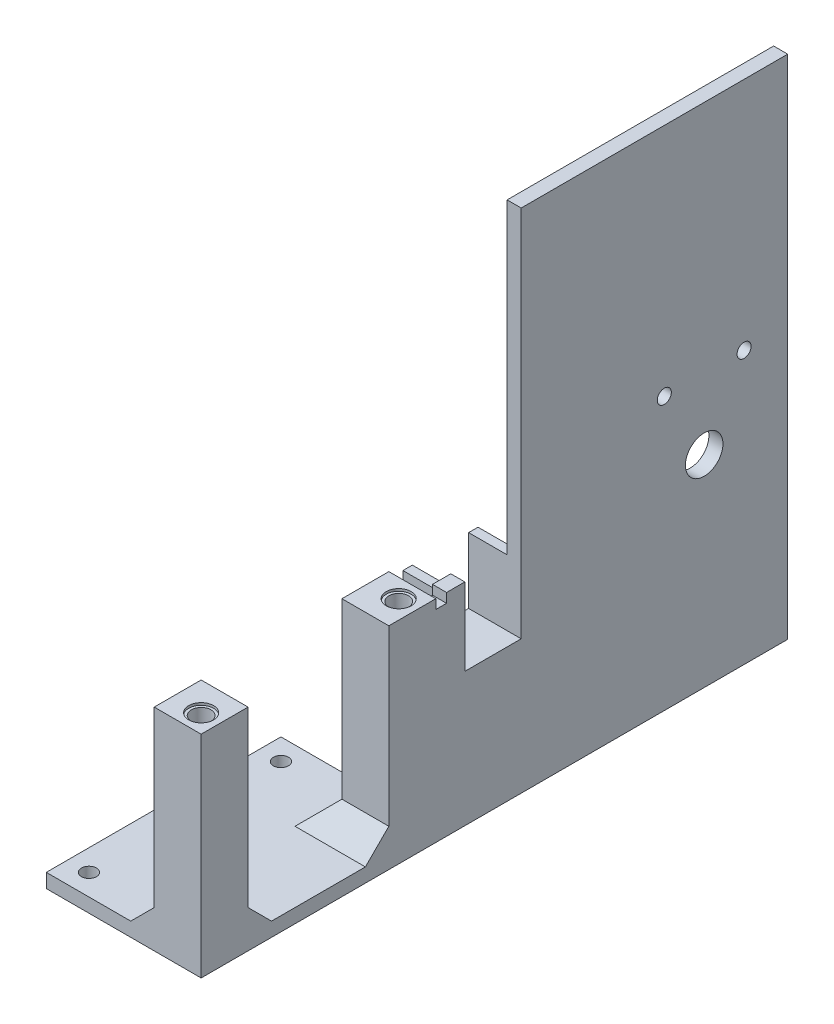
SolidWorks part; units mm, degrees
ref_plane "Front Plane" through (0, 0, 0) normal (0, 0, 1) x (1, 0, 0)
ref_plane "Top Plane" through (0, 0, 0) normal (0, 1, 0) x (1, 0, 0)
ref_plane "Right Plane" through (0, 0, 0) normal (1, 0, 0) x (0, 0, -1)
sketch "Sketch1" plane through (0, 0, 0) normal (0, 1, 0) x (1, 0, 0)
  line L1 (-6.5124, 9.686) -> (1.4876, 9.686)
  line L2 (-6.5124, 9.686) -> (-6.5124, -40.314)
  line L3 (-6.5124, -40.314) -> (1.4876, -40.314)
  line L4 (1.4876, 9.686) -> (1.4876, -40.314)
  line L5 (1.4876, 9.686) -> (26.4876, 9.686)
  line L6 (1.4876, 9.686) -> (1.4876, -40.314)
  line L7 (1.4876, -40.314) -> (26.4876, -40.314)
  line L8 (26.4876, 9.686) -> (26.4876, -40.314)
  circle A0 centre (-1.9624, -35.764) radius 1.6
  circle A1 centre (-1.9624, 5.136) radius 1.6
  dimension "D4" = 3.2
  dimension "D5" = 3.2
  dimension "D6" = 4.55
  dimension "D7" = 4.55
  dimension "D8" = 4.55
  dimension "D9" = 4.55
  dimension "D1" = 8
  dimension "D2" = 50
  dimension "D3" = 25
extrude "Boss-Extrude1" add sketch "Sketch1" along normal blind 3 contours A1 | A0 | L5 L8 L7 L3 L2 L1
sketch "Sketch2" plane through (0, 3, 0) normal (0, 1, 0) x (1, 0, 0)
  line L1 (26.4876, -40.314) -> (16.4876, -40.314)
  line L2 (26.4876, -40.314) -> (26.4876, -30.314)
  line L3 (26.4876, -30.314) -> (16.4876, -30.314)
  line L4 (16.4876, -40.314) -> (16.4876, -30.314)
  line L5 (26.4876, 9.686) -> (16.4876, 9.686)
  line L6 (26.4876, 9.686) -> (26.4876, -0.314)
  line L7 (26.4876, -0.314) -> (16.4876, -0.314)
  line L8 (16.4876, 9.686) -> (16.4876, -0.314)
  dimension "D1" = 10
  dimension "D2" = 10
  dimension "D3" = 10
  dimension "D4" = 10
extrude "Boss-Extrude2" add sketch "Sketch2" along normal blind 42
chamfer "Chamfer1" distance 5 angle 45 4 edges at (16.4876, 3, -4.686) (21.4876, 3, 0.314) (16.4876, 3, 35.314) (21.4876, 3, 30.314)
ref_plane "Plane1" through (0, 45, 0) normal (0, 1, 0) x (1, 0, 0)
sketch "Sketch3" plane through (0, 45, 0) normal (0, 1, 0) x (1, 0, 0)
  line L0 (26.4876, -40.314) -> (26.4876, -30.314) construction
  line L1 (16.4876, -40.314) -> (26.4876, -40.314) construction
  line L2 (26.4876, -0.314) -> (26.4876, 9.686) construction
  line L3 (26.4876, 9.686) -> (16.4876, 9.686) construction
  circle A0 centre (22.5376, -36.364) radius 2.1
  circle A1 centre (22.5376, 5.736) radius 2.1
  dimension "D1" = 4.2
  dimension "D3" = 3.95
  dimension "D4" = 4.2
  dimension "D6" = 3.95
  dimension "D2" = 3.95
  dimension "D5" = 3.95
extrude "Cut-Extrude1" cut sketch "Sketch3" against normal blind 52
sketch "Sketch4" plane through (0, 45, 0) normal (0, 1, 0) x (1, 0, 0)
  circle A0 centre (22.5376, -36.364) radius 2.65
  circle A1 centre (22.5376, 5.736) radius 2.65
  dimension "D1" = 5.3
  dimension "D2" = 5.3
extrude "Cut-Extrude2" cut sketch "Sketch4" against normal blind 0.5
ref_plane "Plane2" through (0, 22.5, 0) normal (0, -1, 0) x (-1, 0, 0)
mirror "Mirror1" about plane through (0, 22.5, 0) normal (0, -1, 0) of "Cut-Extrude2"
sketch "Sketch5" plane through (0, 0, -9.686) normal (0, 0, -1) x (-1, 0, 0)
  line L0 (-26.4876, 45) -> (-26.4876, 0) construction
  line L1 (-26.4876, 43) -> (-23.4876, 43)
  line L2 (-26.4876, 43) -> (-26.4876, 0)
  line L3 (-26.4876, 0) -> (-23.4876, 0)
  line L4 (-23.4876, 43) -> (-23.4876, 0)
  line L5 (6.5124, 0) -> (-26.4876, 0) construction
  line L6 (5.5, 45) -> (-5.5, 45) construction
  dimension "D1" = 3
  dimension "D2" = 2
extrude "Boss-Extrude3" add sketch "Sketch5" along normal blind 75
sketch "Sketch6" plane through (0, 43, 0) normal (0, 1, 0) x (1, 0, 0)
  line L0 (23.4876, 84.686) -> (23.4876, 9.686) construction
  line L1 (23.4876, 11.986) -> (26.4876, 11.986)
  line L2 (23.4876, 11.986) -> (23.4876, 84.686)
  line L3 (23.4876, 84.686) -> (26.4876, 84.686)
  line L4 (26.4876, 11.986) -> (26.4876, 84.686)
  line L5 (26.4876, 9.686) -> (16.4876, 9.686) construction
  dimension "D1" = 2.3
extrude "Boss-Extrude4" add sketch "Sketch6" along normal blind 2
sketch "Sketch7" plane through (0, 45, 0) normal (0, 1, 0) x (1, 0, 0)
  line L0 (26.4876, 11.986) -> (26.4876, 84.686) construction
  line L1 (23.4876, 84.686) -> (26.4876, 84.686)
  line L2 (23.4876, 84.686) -> (23.4876, 15.886)
  line L3 (23.4876, 15.886) -> (26.4876, 15.886)
  line L4 (26.4876, 84.686) -> (26.4876, 15.886)
  line L5 (23.4876, 11.986) -> (26.4876, 11.986) construction
  dimension "D1" = 3.9
extrude "Boss-Extrude5" add sketch "Sketch7" along normal blind 3
sketch "Sketch8" plane through (23.4876, 0, 0) normal (-1, 0, 0) x (0, 0, 1)
  line L0 (-84.686, 48) -> (-15.886, 48) construction
  line L1 (-15.886, 28.5) -> (-27.886, 28.5)
  line L2 (-15.886, 28.5) -> (-15.886, 22.5)
  line L3 (-15.886, 22.5) -> (-27.886, 22.5)
  line L4 (-27.886, 28.5) -> (-27.886, 22.5)
  line L5 (-15.886, 48) -> (-15.886, 45) construction
  line L6 (-15.886, 24.5) -> (-27.886, 24.5) construction
  line L7 (-15.886, 28.5) -> (-15.886, 42.5)
  line L8 (-27.886, 22.5) -> (-29.886, 22.5)
  line L9 (-27.886, 22.5) -> (-27.886, 42.5)
  line L10 (-27.886, 42.5) -> (-29.886, 42.5)
  line L11 (-29.886, 22.5) -> (-29.886, 42.5)
  line L12 (-15.886, 22.5) -> (-13.886, 22.5)
  line L13 (-15.886, 22.5) -> (-15.886, 42.5)
  line L14 (-15.886, 42.5) -> (-13.886, 42.5)
  line L15 (-13.886, 22.5) -> (-13.886, 42.5)
  circle A0 centre (-21.886, 24.5) radius 1
  dimension "D5" = 2
  dimension "D1" = 19.5
  dimension "D2" = 6
  dimension "D3" = 12
  dimension "D4" = 2
  dimension "D6" = 2
  dimension "D7" = 2
  dimension "D8" = 20
extrude "Boss-Extrude7" add sketch "Sketch8" along normal blind 8.2 contours L11 L8 L9 L4 L10 | L6 L2 L1 L4 A0 | L13 L6 A0 L9 L3 | L12 L15 L14 L7 L2 L13 region at (23.4876, 26.5533, -21.886) region at (23.4876, 32.5, -14.886) region at (23.4876, 32.5, -28.886) region at (23.4876, 23.4597, -21.886)
sketch "Sketch9" plane through (23.4876, 0, 0) normal (-1, 0, 0) x (0, 0, 1)
  line L0 (-84.686, 48) -> (-15.886, 48) construction
  line L1 (-15.886, 28.5) -> (-27.886, 28.5)
  line L2 (-15.886, 28.5) -> (-15.886, 48)
  line L3 (-15.886, 48) -> (-27.886, 48)
  line L4 (-27.886, 28.5) -> (-27.886, 48)
extrude "Cut-Extrude3" cut sketch "Sketch9" against normal blind 8.5
sketch "Sketch10" plane through (0, 48, 0) normal (0, 1, 0) x (1, 0, 0)
  line L1 (23.4876, 84.686) -> (26.4876, 84.686)
  line L2 (23.4876, 84.686) -> (23.4876, 27.886)
  line L3 (23.4876, 27.886) -> (26.4876, 27.886)
  line L4 (26.4876, 84.686) -> (26.4876, 27.886)
extrude "Boss-Extrude8" add sketch "Sketch10" along normal blind 15
sketch "Sketch11" plane through (26.4876, 0, 0) normal (1, 0, 0) x (0, 0, -1)
  circle A1 centre (66.886, 43) radius 4
  dimension "D1" = 8
sketch "Sketch12" plane through (26.4876, 0, 0) normal (1, 0, 0) x (0, 0, -1)
  circle A0 centre (58.386, 58) radius 1.5
  circle A1 centre (75.386, 58) radius 1.5
extrude "Cut-Extrude6" cut sketch "Sketch11" against normal blind 3 contours A1
extrude "Cut-Extrude7" cut sketch "Sketch12" against normal blind 3
sketch "Sketch13" plane through (0, 63, 0) normal (0, 1, 0) x (1, 0, 0)
  line L1 (23.4876, 27.886) -> (26.4876, 27.886)
  line L2 (23.4876, 27.886) -> (23.4876, 84.686)
  line L3 (23.4876, 84.686) -> (26.4876, 84.686)
  line L4 (26.4876, 27.886) -> (26.4876, 84.686)
extrude "Boss-Extrude9" add sketch "Sketch13" along normal blind 45
